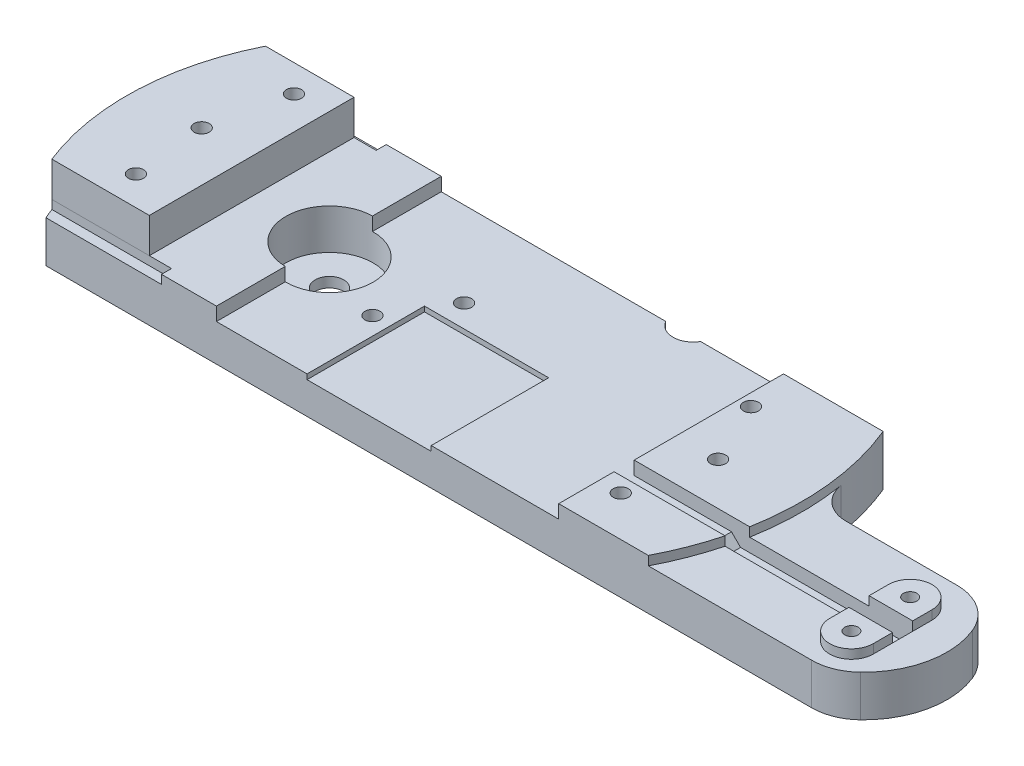
SolidWorks part; units mm, degrees
material "1060 Alloy"
ref_plane "Front Plane" through (0, 0, 0) normal (0, 0, 1) x (1, 0, 0)
ref_plane "Top Plane" through (0, 0, 0) normal (0, 1, 0) x (1, 0, 0)
ref_plane "Right Plane" through (0, 0, 0) normal (1, 0, 0) x (0, 0, -1)
sketch "Sketch1" plane through (0, 0, 0) normal (0, 1, 0) x (1, 0, 0)
  line L1 (-97.5, -33.5) -> (97.5, -33.5)
  line L2 (-97.5, -33.5) -> (-97.5, 33.5)
  line L3 (-97.5, 33.5) -> (97.5, 33.5)
  line L4 (97.5, -33.5) -> (97.5, 33.5)
  line L5 (-97.5, -33.5) -> (97.5, 33.5) construction
  line L6 (-97.5, 33.5) -> (97.5, -33.5) construction
  point P0 (0, 0)
  dimension "D1" = 67
  dimension "D2" = 195
extrude "Boss-Extrude1" add sketch "Sketch1" along normal blind 25.4
sketch "Sketch2" plane through (0, 0, 0) normal (0, -1, 0) x (1, 0, 0)
  line L0 (-97.5, -33.5) -> (-97.5, 33.5) construction
  line L1 (97.5, 33.5) -> (97.5, -33.5) construction
  line L2 (97.5, 33.5) -> (88.5, 33.5)
  line L3 (-97.5, 33.5) -> (97.5, 33.5) construction
  line L4 (97.5, -33.5) -> (91.5, -33.5)
  line L5 (97.5, -33.5) -> (-97.5, -33.5) construction
  line L6 (-97.5, 33.5) -> (-91, 33.5)
  line L7 (-97.5, -33.5) -> (-88, -33.5)
  circle A0 centre (18.0922, -3.2198) radius 79.4078
  circle A1 centre (-22.6589, 2.9929) radius 74.8411
  line M7 (97.5, -33.5) -> (97.5, 33.5)
  line M8 (97.5, 33.5) -> (-97.5, 33.5)
  line M9 (-97.5, 33.5) -> (-97.5, -33.5)
  line M10 (-97.5, -33.5) -> (97.5, -33.5)
  dimension "D1" = 9
  dimension "D2" = 6
  dimension "D3" = 6.5
  dimension "D4" = 9.5
extrude "Cut-Extrude1" cut sketch "Sketch2" against normal through all contours A0 M7 M8 | A0 M10 M7 | A1 M9 M10 | A1 M8 M9 region at (94.8284, 0, 24.4273) region at (95.7123, 0, -25.9883) region at (-95.5654, 0, 25.941) region at (-94.6839, 0, -24.4966)
sketch "Sketch3" plane through (0, 0, 33.5) normal (0, 0, -1) x (-1, 0, 0)
  line L0 (97.5, 25.4) -> (63.2, 25.4)
  line L2 (63.2, 25.4) -> (63.2, 15)
  line L3 (63.2, 15) -> (40.2, 15)
  line L4 (40.2, 15) -> (40.2, 11)
  line L5 (40.2, 11) -> (-61.8, 11)
  line L6 (-91.5, 25.4) -> (88, 25.4) construction
  line L10 (97.5, 0) -> (97.5, 25.4) construction
  line L11 (-61.8, 11) -> (-61.8, 15)
  line L12 (-61.8, 15) -> (-97.5, 15)
  line L13 (-97.5, 25.4) -> (-97.5, 0) construction
  line L14 (-97.5, 15) -> (-97.5, 25.4)
  line L15 (-97.5, 25.4) -> (63.2, 25.4)
  line M13 (-88.5, 0) -> (-88.5, 25.4)
  line M14 (-88.5, 25.4) -> (91, 25.4)
  dimension "D1" = 10.4
  dimension "D2" = 34.3
  dimension "D3" = 23
  dimension "D4" = 4
  dimension "D5" = 102
extrude "Cut-Extrude2" cut sketch "Sketch3" along normal through all contours L11 L12 L2 L3 L4 L5 M13 M14 | L2 L3 L4 L5 L11 L12 L14 L15 region at (12.2699, 18.7206, 33.5)
sketch "Sketch4" plane through (0, 25.4, 0) normal (0, 1, 0) x (1, 0, 0)
  line L0 (-56.5873, 33.5) -> (-56.5873, 30.5)
  line L1 (-63.2, 33.5) -> (-88, 33.5) construction
  line L2 (-56.5873, 30.5) -> (-89.5873, 30.5)
  line L3 (-56.5873, -33.5) -> (-56.5873, -30.5)
  line L4 (-91, -33.5) -> (-63.2, -33.5) construction
  line L5 (-56.5873, -30.5) -> (-92.2617, -30.5)
  line L6 (-56.5873, 33.5) -> (-63.2, 33.5)
  line L7 (-56.5873, -33.5) -> (-63.2, -33.5)
  arc A0 (-88, 33.5) -> (-91, -33.5) centre (-22.6589, -2.9929) ccw construction
  line M5 (-91, -33.5) -> (-63.2, -33.5)
  line M6 (-63.2, -33.5) -> (-63.2, 33.5)
  line M7 (-63.2, 33.5) -> (-88, 33.5)
  arc M8 (-88, 33.5) -> (-91, -33.5) centre (-22.6589, -2.9929) ccw
  dimension "D1" = 3
  dimension "D2" = 3
  dimension "D3" = 33
extrude "Cut-Extrude3" cut sketch "Sketch4" against normal blind 13 contours L2 M6 M7 M8 | L0 L6 L2 M6 | L5 M6 M8 M5 | L7 L3 L5 M6 region at (-59.8937, 25.4, -32) region at (-76.0082, 25.4, -31.9845) region at (-77.4242, 25.4, 31.9889) region at (-59.8937, 25.4, 32)
sketch "Sketch6" plane through (0, 0, 0) normal (0, -1, 0) x (1, 0, 0)
  line L0 (-63.2, -33.5) -> (-97.5, -33.5)
  line L1 (91.5, -33.5) -> (-88, -33.5) construction
  line L2 (-63.2, -33.5) -> (-63.2, 33.5)
  line L3 (-91, 33.5) -> (88.5, 33.5) construction
  line L4 (-63.2, -9) -> (-28.1, -9) construction
  line L5 (-63.2, 8.7) -> (-18.5, 8.7) construction
  line L6 (-63.2, -8.2) -> (-8.1, -8.2) construction
  line L8 (91.5, -33.5) -> (-88, -33.5) construction
  line L9 (-97.5, -33.5) -> (-97.5, 33.5)
  line L10 (-97.5, 33.5) -> (-63.2, 33.5)
  circle A1 centre (-18.5, 8.7) radius 2.25
  circle A2 centre (74.1, -1.7) radius 2.25
  circle A3 centre (68.3, 21.5) radius 2.25
  circle A4 centre (65.4, -20.2) radius 2.25
  circle A5 centre (-8.1, -8.2) radius 2.25
  circle A6 centre (-75.9, 21.8) radius 2.25
  circle A7 centre (-78, 0.1) radius 2.25
  circle A8 centre (-73, -22.4) radius 2.25
  arc A10 (-91, 33.5) -> (-88, -33.5) centre (-22.6589, 2.9929) ccw construction
  dimension "D22" = 4.5
  dimension "D3" = 35.1
  dimension "D4" = 34.3
  dimension "D5" = 44.7
  dimension "D6" = 24.5
  dimension "D7" = 55.1
  dimension "D8" = 42.2
  dimension "D9" = 137.3
  dimension "D10" = 128.6
  dimension "D11" = 131.5
  dimension "D12" = 9.8
  dimension "D13" = 14.8
  dimension "D14" = 12.7
  dimension "D15" = 11.1
  dimension "D16" = 33.6
  dimension "D17" = 55.3
  dimension "D18" = 31.8
  dimension "D19" = 55
  dimension "D20" = 13.3
  dimension "D21" = 25.3
extrude "Cut-Extrude4" cut sketch "Sketch6" against normal through all contours A5 | A1 | A6 | A7 | A8 | A4 | A2 | A3 region at (-18.5, 0, 8.7) region at (74.1, 0, -1.7) region at (68.3, 0, 21.5) region at (65.4, 0, -20.2) region at (-8.1, 0, -8.2) region at (-75.9, 0, 21.8) region at (-78, 0, 0.1) region at (-73, 0, -22.4)
sketch "Sketch7" plane through (0, 11, 0) normal (0, 1, 0) x (1, 0, 0)
  line L1 (-13.2, 1.5) -> (23.8, 1.5)
  line L2 (-13.2, 1.5) -> (-13.2, -33.5)
  line L3 (-13.2, -33.5) -> (23.8, -33.5)
  line L4 (23.8, 1.5) -> (23.8, -33.5)
  line L8 (-63.2, 30.5) -> (-63.2, -30.5) construction
  line L9 (-63.2, 30.5) -> (-63.2, -30.5) construction
  line L10 (-40.2, -33.5) -> (61.8, -33.5) construction
  dimension "D1" = 50
  dimension "D2" = 87
  dimension "D3" = 35
extrude "Cut-Extrude5" cut sketch "Sketch7" against normal blind 1.5
sketch "Sketch8" plane through (0, 25.4, 0) normal (0, 1, 0) x (1, 0, 0)
  line L0 (-56.5873, -33.5) -> (-97.5, -33.5)
  line L1 (-97.5, -33.5) -> (-97.5, 33.5)
  line L3 (-97.5, 33.5) -> (31.9, 33.5)
  line L6 (31.9, 36.5) -> (31.9, 30.5)
  line L7 (31.9, 33.5) -> (37.0962, 33.5)
  line L10 (-56.5873, 33.5) -> (-88, 33.5) construction
  line L11 (-40.2, 33.5) -> (61.8, 33.5) construction
  circle A1 centre (31.9, 36.5) radius 6
  arc A2 (-89.5873, 30.5) -> (-92.2617, -30.5) centre (-22.6589, -2.9929) ccw construction
  dimension "D1" = 12
  dimension "D2" = 129.4
extrude "Cut-Extrude6" cut sketch "Sketch8" against normal blind 18.5 contours L6 A1 L7 | L3 A1 L6 region at (29.8648, 25.4, -32.2699) region at (33.9352, 25.4, -32.2699)
sketch "Sketch9" plane through (0, 0, 0) normal (0, -1, 0) x (1, 0, 0)
  line L0 (88.5, 33.5) -> (137.2004, 33.5)
  line L1 (139.5727, -7.5) -> (97.3846, -7.5)
  arc A0 (153.4738, 1.8643) -> (147.5429, 29.3643) centre (130.3054, 11.2571) ccw
  arc A1 (91.5, -33.5) -> (88.5, 33.5) centre (18.0922, -3.2198) ccw construction
  arc A2 (142.3827, -10.6321) -> (147.5429, 29.3643) centre (130.3054, 11.2571) ccw construction
  arc A3 (147.5429, 29.3643) -> (137.2004, 33.5) centre (137.2004, 18.5) ccw
  arc A4 (147.5429, 29.3643) -> (137.9704, 33.4802) centre (137.2004, 18.5) ccw construction
  arc A5 (139.5727, -7.5) -> (153.4738, 1.8643) centre (139.5727, 7.5) ccw
  circle A6 centre (112.8948, -27.5) radius 16 construction
  circle A7 centre (103.4238, 59.4942) radius 16 construction
  circle A8 centre (112.8948, -27.5) radius 20 construction
  arc A9 (97.3846, -7.5) -> (88.5, 33.5) centre (18.0922, -3.2198) ccw
  circle A10 centre (138.3, 5.25) radius 2
  circle A11 centre (138.3, 22.75) radius 2
  circle A12 centre (138.3, 22.75) radius 2 construction
  circle A13 centre (138.3, 5.25) radius 2 construction
  dimension "D1" = 4
extrude "Boss-Extrude2" add sketch "Sketch9" against normal offset from surface (12.3 mm away) 1.3 up to face at (-16.25, 11, 8.7) offset beyond the face yes
fillet "Fillet1" radius 10 1 edges at (97.3846, 6.15, -7.5)
sketch "Sketch10" plane through (0, 0, 0) normal (0, -1, 0) x (1, 0, 0)
  circle A0 centre (-40.0178, 0) radius 13
  point P3 (-40.0178, 0)
  dimension "D1" = 26
extrude "Cut-Extrude7" cut sketch "Sketch10" against normal up to surface (15 mm away) from offset 3 up to face at (-54.1437, 15, 0) offset against normal yes
sketch "Sketch13" plane through (0, 0, 0) normal (0, -1, 0) x (1, 0, 0)
  circle A0 centre (-40.0178, 0) radius 4.25
  dimension "D1" = 8.5
extrude "Cut-Extrude9" cut sketch "Sketch13" against normal through all
sketch "Sketch11" plane through (0, 12.3, 0) normal (0, 1, 0) x (1, 0, 0)
  line L0 (138.3, -5.25) -> (138.3, -22.75) construction
  line L1 (144.8, -5.25) -> (144.8, -22.75)
  line L2 (131.8, -5.25) -> (131.8, -22.75)
  line L3 (131.8, -11) -> (144.8, -11)
  line L4 (131.8, -17) -> (144.8, -17)
  line L5 (131.8, -14) -> (144.8, -14) construction
  arc A0 (144.8, -5.25) -> (131.8, -5.25) centre (138.3, -5.25) ccw
  arc A1 (131.8, -22.75) -> (144.8, -22.75) centre (138.3, -22.75) ccw
  point P4 (138.3, -14)
  circle M15 centre (138.3, -22.75) radius 2
  circle M16 centre (138.3, -5.25) radius 2
  dimension "D1" = 13
  dimension "D2" = 6
extrude "Boss-Extrude3" add sketch "Sketch11" along normal up to surface (2.7 mm away) contours L1 A0 L2 L3 M16 | L2 A1 L1 L4 M15 region at (144.6214, 12.3, 8.125) region at (144.6214, 12.3, 19.875) up to face at (70.55, 15, 21.5)
sketch "Sketch12" plane through (0, 0, 11) normal (0, 0, 1) x (1, 0, 0)
  line L0 (144.8, 15) -> (144.8, 8.3)
  line L1 (144.8, 8.3) -> (93.5, 8.3)
  line L3 (97.5, 12.3) -> (88.5, 12.3) construction
  line L4 (90.8, 11) -> (61.8, 11)
  line L5 (61.8, 11) -> (61.8, 15)
  line L6 (61.8, 15) -> (88.5, 15) construction
  line L7 (61.8, 15) -> (144.8, 15)
  line L10 (97.5, 12.3) -> (93.5, 12.3) construction
  line L12 (88.5, 12.3) -> (137.2004, 12.3) construction
  line L13 (93.5, 12.3) -> (93.5, 8.3) construction
  line L14 (61.8, 11) -> (61.8, 15) construction
  line L15 (23.8, 11) -> (61.8, 11) construction
  line L16 (93.5, 8.3) -> (90.8, 11)
  dimension "D1" = 45
extrude "Cut-Extrude8" cut sketch "Sketch12" along normal up to surface (6 mm away) up to face at (138.3, 13.65, 17)
split "Split1" bodies to split 116 resulting bodies 114 115 split by face at (-52.6367, 15, 0)
